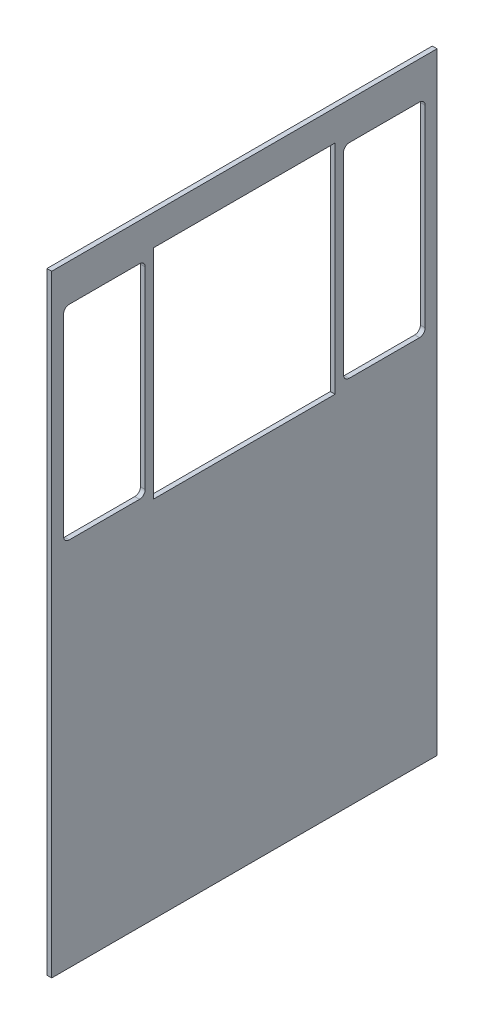
SolidWorks part; units mm, degrees
material "ASTM A36 Steel"
ref_plane "Front Plane" through (0, 0, 0) normal (0, 0, 1) x (1, 0, 0)
ref_plane "Top Plane" through (0, 0, 0) normal (0, 1, 0) x (1, 0, 0)
ref_plane "Right Plane" through (0, 0, 0) normal (1, 0, 0) x (0, 0, -1)
sketch "Sketch1" plane through (0, 0, 0) normal (1, 0, 0) x (0, 0, -1)
  line L0 (0, 0) -> (0, 349.25) construction
  line L1 (98.1075, 207.645) -> (58.7375, 207.645)
  line L2 (114.3, 0) -> (-114.3, 0)
  line L3 (114.3, 0) -> (114.3, 349.25)
  line L4 (114.3, 349.25) -> (-114.3, 349.25)
  line L5 (-114.3, 0) -> (-114.3, 349.25)
  line L6 (114.3, 0) -> (-114.3, 349.25) construction
  line L7 (114.3, 349.25) -> (-114.3, 0) construction
  line L8 (50.8, 203.835) -> (-50.8, 203.835)
  line L9 (50.8, 203.835) -> (50.8, 325.755)
  line L10 (50.8, 325.755) -> (-50.8, 325.755)
  line L11 (-50.8, 203.835) -> (-50.8, 325.755)
  line L12 (50.8, 203.835) -> (-50.8, 325.755) construction
  line L13 (50.8, 325.755) -> (-50.8, 203.835) construction
  line L14 (-98.1075, 207.645) -> (-58.7375, 207.645)
  line L15 (-101.2825, 210.82) -> (-101.2825, 318.77)
  line L16 (-98.1075, 321.945) -> (-58.7375, 321.945)
  line L17 (-55.5625, 210.82) -> (-55.5625, 318.77)
  line L18 (98.1075, 321.945) -> (58.7375, 321.945)
  line L19 (55.5625, 210.82) -> (55.5625, 318.77)
  line L20 (101.2825, 210.82) -> (101.2825, 318.77)
  arc A6 (-55.5625, 210.82) -> (-58.7375, 207.645) centre (-58.7375, 210.82) cw
  arc A7 (-101.2825, 210.82) -> (-98.1075, 207.645) centre (-98.1075, 210.82) ccw
  arc A8 (-98.1075, 321.945) -> (-101.2825, 318.77) centre (-98.1075, 318.77) ccw
  arc A9 (-58.7375, 321.945) -> (-55.5625, 318.77) centre (-58.7375, 318.77) cw
  arc A10 (98.1075, 321.945) -> (101.2825, 318.77) centre (98.1075, 318.77) cw
  arc A11 (58.7375, 321.945) -> (55.5625, 318.77) centre (58.7375, 318.77) ccw
  arc A12 (55.5625, 210.82) -> (58.7375, 207.645) centre (58.7375, 210.82) ccw
  arc A13 (101.2825, 210.82) -> (98.1075, 207.645) centre (98.1075, 210.82) cw
  point P3 (0, 174.625)
  point P14 (0, 264.795)
  point P39 (-101.2825, 207.645)
  point P42 (-101.2825, 321.945)
  dimension "D5" = 121.92
  dimension "D12" = 3.175
  dimension "D8" = 114.3
  dimension "D1" = 349.25
  dimension "D2" = 228.6
  dimension "D4" = 101.6
  dimension "D6" = 23.495
  dimension "D9" = 45.72
  dimension "D10" = 27.305
  dimension "D11" = 55.5625
extrude "Boss-Extrude1" add sketch "Sketch1" along normal blind 2.667
sketch "Sketch2" plane through (2.667, 0, 0) normal (1, 0, 0) x (0, 0, -1)
  line L0 (-114.3, 349.25) -> (-114.3, 0) construction
  line L1 (114.3, 349.25) -> (-114.3, 349.25) construction
  line L2 (114.3, 0) -> (114.3, 349.25) construction
  line L3 (-114.3, 349.25) -> (-114.3, 0)
  line L4 (114.3, 349.25) -> (-114.3, 349.25)
  line L5 (114.3, 0) -> (114.3, 349.25)
  line L6 (107.95, 0) -> (107.95, 342.9)
  line L7 (107.95, 342.9) -> (-107.95, 342.9)
  line L8 (-107.95, 342.9) -> (-107.95, 0)
  line M9 (-114.3, 349.25) -> (-114.3, 0)
  line M10 (-114.3, 0) -> (114.3, 0)
  line M11 (114.3, 0) -> (114.3, 349.25)
  line M12 (114.3, 349.25) -> (-114.3, 349.25)
  dimension "D1" = 6.35
extrude "CornerRadiusAllowance" cut sketch "Sketch2" against normal through all contours L8 L7 L6 M10 M11 M12 M9 region at (2.667, 345.0759, 0)
